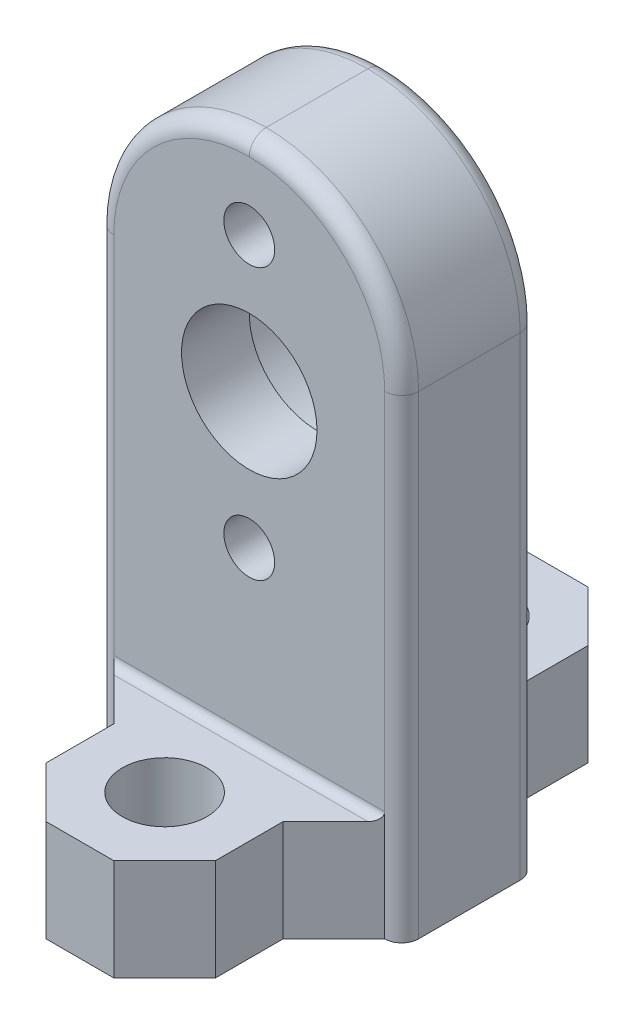
SolidWorks part; units mm, degrees
ref_plane "Front Plane" through (0, 0, 0) normal (0, 0, 1) x (1, 0, 0)
ref_plane "Top Plane" through (0, 0, 0) normal (0, 1, 0) x (1, 0, 0)
ref_plane "Right Plane" through (0, 0, 0) normal (1, 0, 0) x (0, 0, -1)
sketch "Sketch1" plane through (0, 0, 0) normal (0, 0, 1) x (1, 0, 0)
  line L1 (-9, 13) -> (9, 13)
  line L2 (-9, 13) -> (-9, -24)
  line L4 (9, 13) -> (9, -24)
  line L5 (-9, 13) -> (9, -15) construction
  line L6 (-9, -15) -> (9, 13) construction
  line L9 (-9, -24) -> (9, -24)
  circle A0 centre (0, 0) radius 6
  point P0 (0, 0)
  dimension "D7" = 12
  dimension "D1" = 9
  dimension "D2" = 13
  dimension "D4" = 18
  dimension "D5" = 24
extrude "Boss-Extrude1" add sketch "Sketch1" along normal blind 8 contours L4 L1 L2 L9 A0 | A0 region at (0, -6.625, 0) region at (0, 0, 0)
extrude "Cut-Extrude1" cut sketch "Sketch1<3>" along normal blind 4 contours A0 region at (0, 0, 0)
sketch "Sketch1<3>" plane through (0, 0, 0) normal (0, 0, 1) x (1, 0, 0) same geometry as "Sketch1"
sketch "Sketch2" plane through (0, 0, 8) normal (0, 0, 1) x (1, 0, 0)
  circle A0 centre (0, 0) radius 4
  dimension "D1" = 8
extrude "Cut-Extrude2" cut sketch "Sketch2" against normal up to surface (4 mm away) up to face at (6, 0, 4)
fillet "Fillet1" radius 9 2 edges at (-9, 13, 4) (9, 13, 4)
sketch "Sketch3" plane through (0, -24, 0) normal (0, -1, 0) x (1, 0, 0)
  line L0 (-9, 4) -> (9, 4) construction
  line L1 (-9, 8) -> (-9, 0) construction
  line L2 (9, 8) -> (9, 0) construction
  line L3 (-9, 8) -> (9, 8) construction
  line L4 (5, -10) -> (-5, -10)
  line L5 (5, -10) -> (5, 18)
  line L6 (5, 18) -> (-5, 18)
  line L7 (-5, -10) -> (-5, 18)
  line L8 (5, -10) -> (-5, 18) construction
  line L9 (5, 18) -> (-5, -10) construction
  circle A0 centre (0, 13) radius 2.5
  circle A1 centre (0, -5) radius 2.5
  point P6 (0, 4)
  dimension "D3" = 5
  dimension "D1" = 10
  dimension "D2" = 28
  dimension "D4" = 5
extrude "Boss-Extrude2" add sketch "Sketch3" against normal blind 6
fillet "Fillet3" radius 0.5 2 edges at (0, -18, 0) (0, -18, 8)
fillet "Fillet5" radius 1 8 edges at (6.364, 10.364, 0) (-6.364, 10.364, 0) (6.364, 10.364, 8) (-6.364, 10.364, 8) (9, -10, 0) (9, -10, 8) (-9, -10, 0) (-9, -10, 8)
sketch "Sketch4" plane through (0, 0, 0) normal (0, 0, -1) x (-1, 0, 0)
  line L0 (0, 0) -> (0, 8) construction
  line L1 (0, 0) -> (0, -8.0157) construction
  circle A2 centre (0, 8) radius 1.5
  circle A4 centre (0, -8) radius 1.5
  point P11 (0, 0)
  dimension "D1" = 3
  dimension "D3" = 180
  dimension "D4" = 2
  dimension "D2" = 8
extrude "Cut-Extrude3" cut sketch "Sketch4" against normal through all
chamfer "Chamfer1" distance 3 angle 45 4 edges at (5, -20.75, 8) (5, -20.75, 0) (-5, -20.75, 0) (-5, -20.75, 8)
chamfer "Chamfer2" distance 3 angle 45 4 edges at (-5, -21, -10) (5, -21, -10) (-5, -21, 18) (5, -21, 18)
